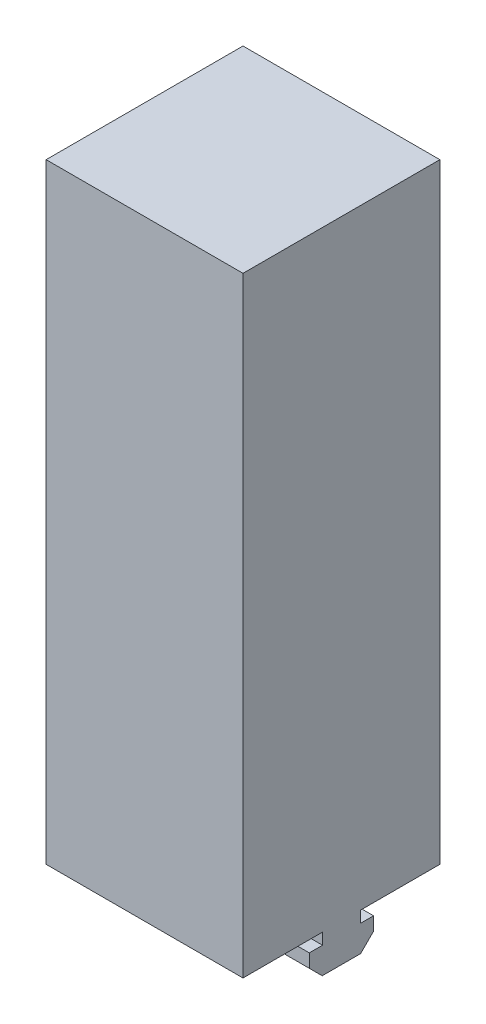
SolidWorks part; units mm, degrees
ref_plane "Front Plane" through (0, 0, 0) normal (0, 0, 1) x (1, 0, 0)
ref_plane "Top Plane" through (0, 0, 0) normal (0, 1, 0) x (1, 0, 0)
ref_plane "Right Plane" through (0, 0, 0) normal (1, 0, 0) x (0, 0, -1)
sketch "Sketch1" plane through (0, 0, 0) normal (0, 0, 1) x (1, 0, 0)
  line L1 (0, 0) -> (31.75, 0)
  line L2 (0, 0) -> (0, 19.05)
  line L3 (0, 19.05) -> (31.75, 19.05)
  line L4 (31.75, 0) -> (31.75, 19.05)
  point P10 (0, 9.525)
  point P12 (15.875, 0)
  dimension "D1" = 31.75
  dimension "D2" = 19.05
extrude "Boss-Extrude1" add sketch "Sketch1" along normal blind 31.75
shell "Shell1" thickness 3.175 removed face at (15.875, 9.525, 0)
sketch "Sketch2" plane through (0, 0, 0) normal (0, -1, 0) x (1, 0, 0)
  line L1 (3.175, 28.575) -> (28.575, 28.575)
  line L2 (3.175, 28.575) -> (3.175, 3.175)
  line L3 (3.175, 3.175) -> (28.575, 3.175)
  line L4 (0, 0) -> (31.75, 0)
  line L5 (31.75, 0) -> (31.75, 31.75)
  line L6 (31.75, 31.75) -> (0, 31.75)
  line L7 (0, 31.75) -> (0, 0)
  line L8 (0, 0) -> (31.75, 0)
  line L9 (31.75, 0) -> (31.75, 31.75)
  line L10 (31.75, 31.75) -> (0, 31.75)
  line L11 (0, 31.75) -> (0, 0)
  line L12 (28.575, 28.575) -> (28.575, 3.175)
  dimension "D2" = 3.175
  dimension "D3" = 3.175
  dimension "D4" = 3.175
  dimension "D1" = 0
extrude "Boss-Extrude2" add sketch "Sketch2" along normal blind 76.2
sketch "Sketch3" plane through (0, 0, 0) normal (1, 0, 0) x (0, 0, -1)
  line L5 (-10.6934, -81.2114) -> (-10.6934, -83.3716)
  line L6 (-10.6934, -83.3716) -> (-12.775, -85.4532)
  line L7 (-12.775, -85.4532) -> (-18.975, -85.4532)
  line L8 (-18.975, -85.4532) -> (-21.0566, -83.3716)
  line L9 (-21.0566, -83.3716) -> (-21.0566, -81.2114)
  line L14 (0, -76.2) -> (-31.75, -76.2)
  line L15 (-31.75, -76.2) -> (-31.75, -79.375)
  line L16 (-31.75, -79.375) -> (-18.923, -79.375)
  line L17 (-18.923, -79.375) -> (-18.923, -81.2114)
  line L18 (-18.923, -81.2114) -> (-21.0566, -81.2114)
  line L19 (-12.827, -79.375) -> (-12.827, -81.2114)
  line L20 (-12.827, -81.2114) -> (-10.6934, -81.2114)
  line L21 (0, -76.2) -> (0, -79.375)
  line L22 (-12.827, -79.375) -> (0, -79.375)
  point P1 (0.3112, -92.075)
  point P20 (-13.2481, -92.075)
  dimension "D1" = 6.2
  dimension "D2" = 6.096
  dimension "D3" = 10.3632
  dimension "D4" = 1.8364
  dimension "D5" = 4.2418
  dimension "D6" = 3.175
extrude "Boss-Extrude3" add sketch "Sketch3" along normal up to surface (31.75 mm away) up to face at (31.75, -28.575, 15.875)
